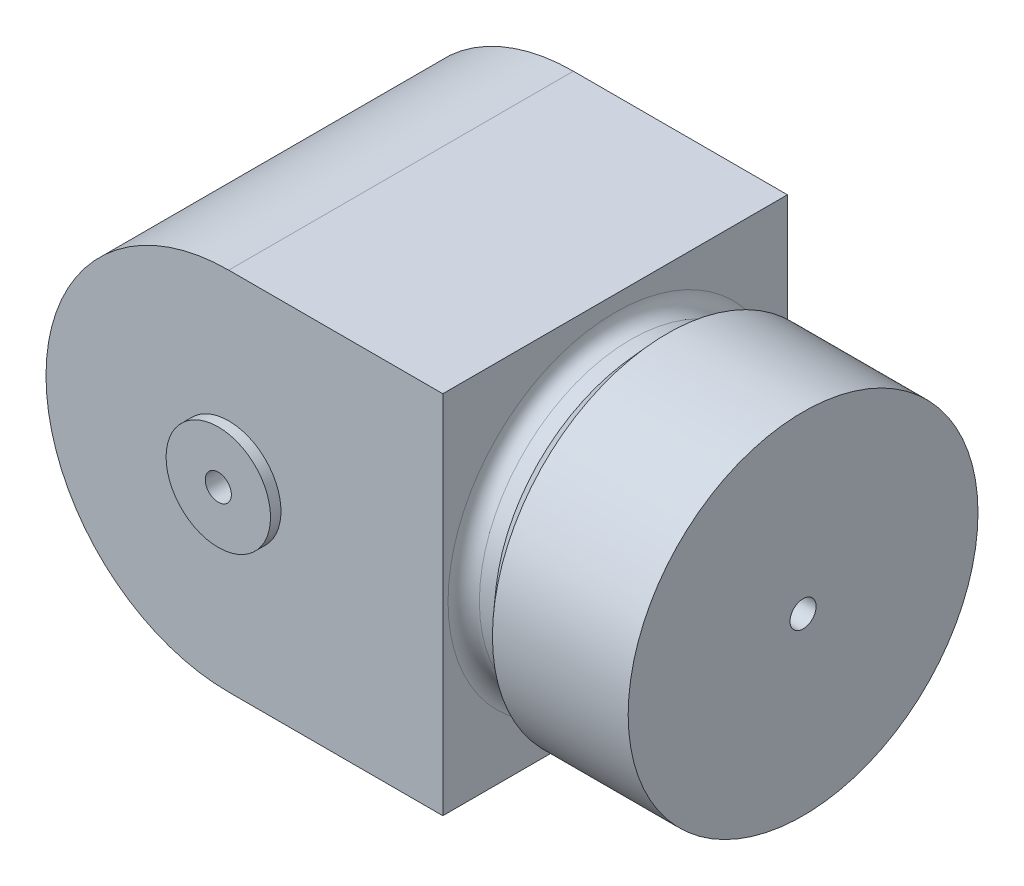
SolidWorks part; units mm, degrees
note: '?' marks a value the reader was unsure of.
ref_plane "正面" through (0, 0, 0) normal (0, 0, 1) x (1, 0, 0)
ref_plane "平面" through (0, 0, 0) normal (0, 1, 0) x (1, 0, 0)
ref_plane "右側面" through (0, 0, 0) normal (1, 0, 0) x (0, 0, -1)
sketch "ｽｹｯﾁ1" plane through (0, 0, 0) normal (0, 0, 1) x (1, 0, 0)
  line L1 (0, 0) -> (76, 0)
  line L2 (0, 0) -> (0, 70)
  line L3 (0, 70) -> (76, 70)
  line L4 (76, 0) -> (76, 70)
  dimension "D1" = 70
  dimension "D2" = 76
extrude "押し出し1" add sketch "ｽｹｯﾁ1" along normal blind 66
sketch "ｽｹｯﾁ2" plane through (0, 0, 66) normal (0, 0, 1) x (1, 0, 0)
  line L0 (-6.0184, 35) -> (85.9436, 35) construction
  line L1 (0, 0) -> (76, 0) construction
  line L2 (0, 70) -> (0, 0) construction
  line L3 (76, 70) -> (0, 70) construction
  line L5 (35, 70) -> (-10.0838, 70)
  line L6 (35, 70) -> (35, 0)
  line L7 (35, 0) -> (-10.0838, 0)
  line L8 (-10.0838, 70) -> (-10.0838, 0)
  circle A0 centre (35, 35) radius 35
  line M1 (0, 70) -> (0, 0)
  line M2 (0, 0) -> (76, 0)
  line M4 (76, 70) -> (0, 70)
  dimension "D1" = 35
  dimension "D2" = 35
extrude "ｶｯﾄ - 押し出し1" cut sketch "ｽｹｯﾁ2" against normal through all contours A0 M1 M4 | A0 M2 M1
sketch "ｽｹｯﾁ3" plane through (0, 0, 66) normal (0, 0, 1) x (1, 0, 0)
  circle A0 centre (35, 35) radius 2.5
  dimension "D1" = 5
extrude "ｶｯﾄ - 押し出し2" cut sketch "ｽｹｯﾁ3" against normal through all
sketch "ｽｹｯﾁ4" plane through (76, 0, 0) normal (1, 0, 0) x (0, 0, -1)
  line L0 (-66, 35) -> (0, 35) construction
  line L1 (-66, 0) -> (-66, 70) construction
  line L2 (0, 0) -> (0, 70) construction
  line L3 (-33, 70) -> (-33, 0) construction
  line L4 (-66, 70) -> (0, 70) construction
  line L5 (-66, 0) -> (0, 0) construction
  circle A0 centre (-33, 35) radius 29
  dimension "D1" = 58
extrude "押し出し2" add sketch "ｽｹｯﾁ4" along normal blind 6
fillet "ﾌｨﾚｯﾄ1" radius 3 1 edges at (76, 35, 62)
sketch "ｽｹｯﾁ5" plane through (82, 0, 0) normal (1, 0, 0) x (0, 0, -1)
  circle A0 centre (-33, 35) radius 33.5
  dimension "D1" = 67
extrude "押し出し3" add sketch "ｽｹｯﾁ5" along normal blind 30
chamfer "面取り2" distance 4 angle 48 1 edges at (82, 35, -0.5)
sketch "ｽｹｯﾁ6" plane through (112, 0, 0) normal (1, 0, 0) x (0, 0, -1)
  circle A0 centre (-33, 35) radius 2.5
  dimension "D1" = 5
extrude "ｶｯﾄ - 押し出し3" cut sketch "ｽｹｯﾁ6" against normal blind 10
sketch "ｽｹｯﾁ7" plane through (0, 0, 66) normal (0, 0, 1) x (1, 0, 0)
  circle A0 centre (35, 35) radius 10
  circle A1 centre (35, 35) radius 2.5
  dimension "D1" = 20
  dimension "D2" = 5
extrude "押し出し4" add sketch "ｽｹｯﾁ7" along normal blind 2
sketch "ｽｹｯﾁ8" plane through (0, 0, 0) normal (0, 0, -1) x (-1, 0, 0)
  circle A0 centre (-35, 35) radius 10
  circle A1 centre (-35, 35) radius 2.5
  dimension "D1" = 20
  dimension "D2" = 5
extrude "押し出し5" add sketch "ｽｹｯﾁ8" along normal blind 2
ref_axis "第五軸回転中心" through (35, 35, -2) along (0, 0, 1)?
ref_axis "第六軸回転中心" through (102, 35, 33) along (1, 0, 0)?
ref_plane "中間平面" through (0, 0, 33) normal (0, 0, 1) x (1, 0, 0)
